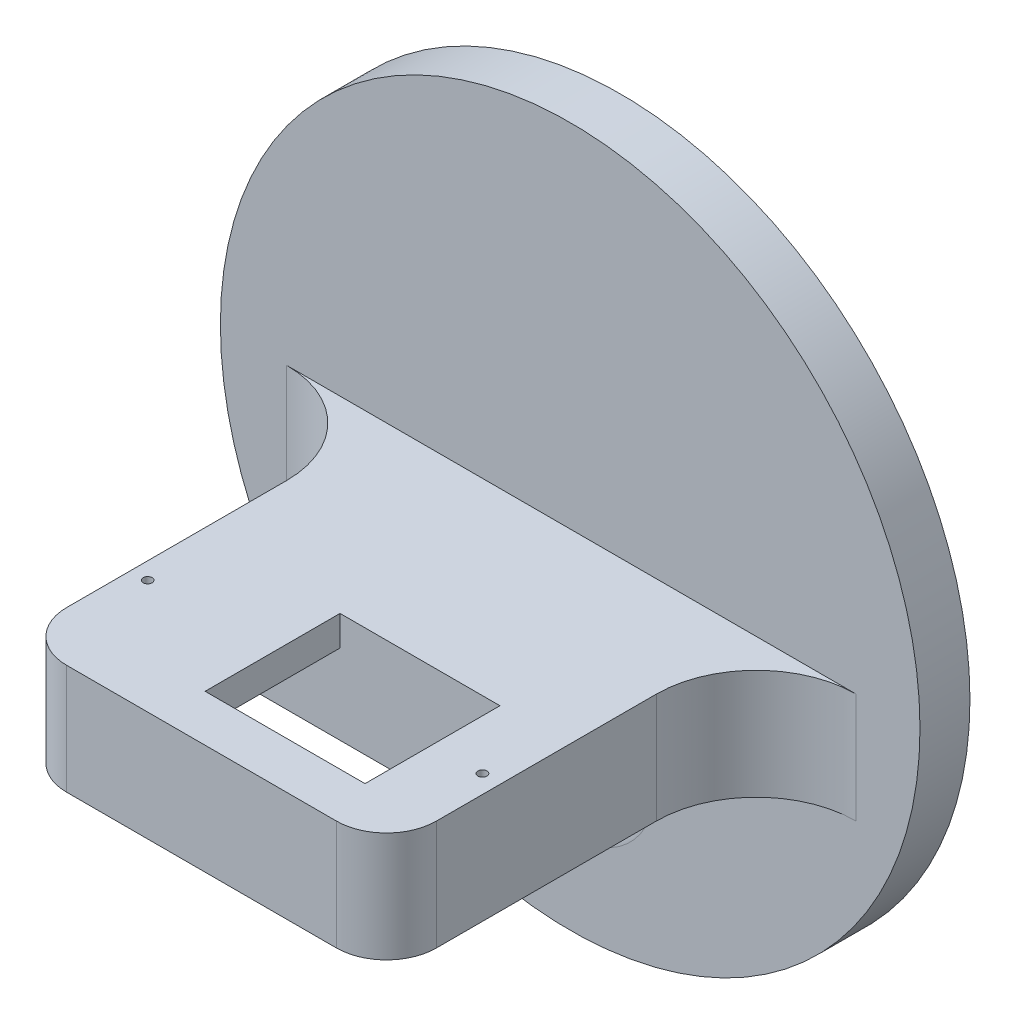
SolidWorks part; units mm, degrees
ref_plane "Front Plane" through (0, 0, 0) normal (0, 0, 1) x (1, 0, 0)
ref_plane "Top Plane" through (0, 0, 0) normal (0, 1, 0) x (1, 0, 0)
ref_plane "Right Plane" through (0, 0, 0) normal (1, 0, 0) x (0, 0, -1)
sketch "Sketch2" plane through (0, 0, 0) normal (0, 0, 1) x (1, 0, 0)
  line L1 (18.613, 2.7758) -> (-18.387, 2.7758)
  line L2 (18.613, 2.7758) -> (18.613, -11.2242)
  line L3 (18.613, -11.2242) -> (-18.387, -11.2242)
  line L4 (-18.387, 2.7758) -> (-18.387, -11.2242)
  line L5 (18.613, 2.7758) -> (-18.387, -11.2242) construction
  line L6 (18.613, -11.2242) -> (-18.387, 2.7758) construction
  circle A0 centre (0, 0) radius 37.5
  point P3 (0.113, -4.2242)
  dimension "D1" = 75
  dimension "D2" = 14
  dimension "D3" = 37
extrude "Boss-Extrude2" add sketch "Sketch2" along normal blind 37 contours L2 L1 L4 L3
sketch "Sketch4" plane through (0, 0, 0) normal (0, 0, -1) x (-1, 0, 0)
  circle A0 centre (0, 0) radius 35
  dimension "D1" = 70
extrude "Boss-Extrude3" add sketch "Sketch4" along normal blind 5
sketch "Sketch5" plane through (0, -11.2242, 0) normal (0, -1, 0) x (-1, 0, 0)
  line L0 (0, 0) -> (0, -35.31)
  line L1 (-17.0481, -32.3266) -> (16.9519, -32.3266)
  line L2 (-17.0481, -32.3266) -> (-17.0481, -18.8266)
  line L3 (-17.0481, -18.8266) -> (16.9519, -18.8266)
  line L4 (16.9519, -32.3266) -> (16.9519, -18.8266)
  line L5 (-17.0481, -32.3266) -> (16.9519, -18.8266) construction
  line L6 (-17.0481, -18.8266) -> (16.9519, -32.3266) construction
  point P0 (-0.0481, -25.5766)
  dimension "D1" = 34
  dimension "D2" = 13.5
extrude "Cut-Extrude1" cut sketch "Sketch5" against normal blind 5 contours L2 L1 L4 L3
sketch "Sketch6" plane through (0, -6.2242, 0) normal (0, -1, 0) x (-1, 0, 0)
  line L0 (-17.0481, -32.3266) -> (16.9519, -32.3266) construction
  line L1 (11.7019, -32.3266) -> (-11.7981, -32.3266)
  line L2 (11.7019, -32.3266) -> (11.7019, -18.8266)
  line L3 (11.7019, -18.8266) -> (-11.7981, -18.8266)
  line L4 (-11.7981, -32.3266) -> (-11.7981, -18.8266)
  line L5 (-17.0481, -18.8266) -> (16.9519, -18.8266) construction
  line L6 (16.9519, -32.3266) -> (16.9519, -18.8266) construction
  dimension "D1" = 23.5
  dimension "D2" = 5.25
extrude "Cut-Extrude2" cut sketch "Sketch6" against normal blind 3
sketch "Sketch7" plane through (0, -11.2242, 0) normal (0, -1, 0) x (-1, 0, 0)
  line L0 (-17.0481, -32.3266) -> (-11.7981, -32.3266) construction
  line L1 (-11.7981, -32.3266) -> (4.2019, -32.3266)
  line L2 (-11.7981, -32.3266) -> (-11.7981, -18.8266)
  line L3 (-11.7981, -18.8266) -> (4.2019, -18.8266)
  line L4 (4.2019, -32.3266) -> (4.2019, -18.8266)
  line L5 (-11.7981, -18.8266) -> (-11.7981, -32.3266) construction
  line L6 (11.7019, -18.8266) -> (-11.7981, -18.8266) construction
  dimension "D1" = 16
extrude "Cut-Extrude3" cut sketch "Sketch7" against normal blind 12
sketch "Sketch8" plane through (0, 0, 37) normal (0, 0, 1) x (1, 0, 0)
  line L0 (18.613, 2.7758) -> (18.613, -11.2242) construction
  line L1 (-18.387, 2.7758) -> (18.613, 2.7758)
  line L2 (-18.387, 2.7758) -> (-18.387, -0.2242)
  line L3 (-18.387, -0.2242) -> (18.613, -0.2242)
  line L4 (18.613, 2.7758) -> (18.613, -0.2242)
  dimension "D1" = 3
extrude "Cut-Extrude4" cut sketch "Sketch8" against normal blind 37
sketch "Sketch9" plane through (0, 0, 0) normal (0, 0, 1) x (1, 0, 0)
  circle A0 centre (0, -18.3393) radius 5.5
  dimension "D1" = 11
extrude "Cut-Extrude5" cut sketch "Sketch9" against normal through all
sketch "Sketch10" plane through (0, -6.2242, 0) normal (0, -1, 0) x (-1, 0, 0)
  line L1 (-17.0481, -32.3266) -> (-11.7981, -32.3266) construction
  line L2 (11.7019, -32.3266) -> (16.9519, -32.3266) construction
  line L4 (16.9519, -32.3266) -> (16.9519, -18.8266) construction
  line L5 (-17.0481, -32.3266) -> (-17.0481, -18.8266) construction
  circle A0 centre (-16.7981, -25.5766) radius 0.425
  circle A1 centre (16.7019, -25.5766) radius 0.25
  point P12 (-17.0481, -25.5766)
  dimension "D3" = 0.85
  dimension "D4" = 0.5
  dimension "D5" = 0.25
  dimension "D6" = 0.25
  dimension "D1" = 6.75
  dimension "D2" = 6.75
extrude "Cut-Extrude6" cut sketch "Sketch10" against normal through all
sketch "Sketch11" plane through (0, -0.2242, 0) normal (0, 1, 0) x (1, 0, 0)
  circle A0 centre (-16.7019, -25.5766) radius 0.45
  circle A1 centre (16.7981, -25.5766) radius 0.45
  dimension "D1" = 0.9
  dimension "D2" = 0.9
extrude "Cut-Extrude7" cut sketch "Sketch11" against normal through all
sketch "Sketch12" plane through (0, 0, -5) normal (0, 0, -1) x (-1, 0, 0)
  circle A0 centre (-12.25, 0) radius 0.125
  circle A1 centre (12.25, 0) radius 0.125
  point P0 (0.5097, -12.2006)
  dimension "D3" = 0.25
  dimension "D4" = 0.25
  dimension "D1" = 12.25
  dimension "D2" = 12.25
fillet "Fillet1" radius 10 2 edges at (18.613, -5.7242, 0) (-18.387, -5.7242, 0)
fillet "Fillet2" radius 5 2 edges at (18.613, -5.7242, 37) (-18.387, -5.7242, 37)
fillet "Fillet4" radius 3 1 edges at (5.5, -18.3393, 0)
